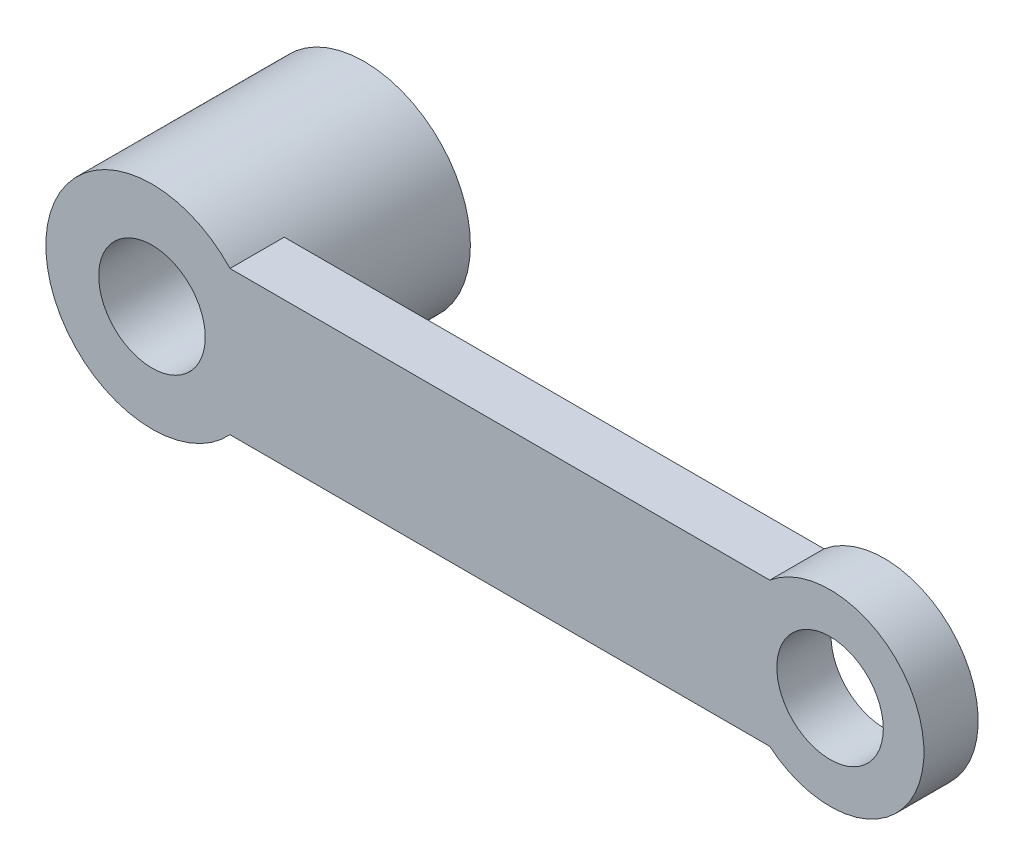
SolidWorks part; units mm, degrees
ref_plane "Alzado" through (0, 0, 0) normal (0, 0, 1) x (1, 0, 0)
ref_plane "Planta" through (0, 0, 0) normal (0, 1, 0) x (1, 0, 0)
ref_plane "Vista lateral" through (0, 0, 0) normal (1, 0, 0) x (0, 0, -1)
sketch "Croquis1" plane through (0, 0, 0) normal (0, 0, 1) x (1, 0, 0)
  line L1 (7.478, 6.9) -> (59.2216, 6.9)
  line L3 (7.478, -6.9) -> (59.2216, -6.9)
  circle A0 centre (0, 0) radius 5.105
  circle A1 centre (0, 0) radius 10.175
  circle A2 centre (65, 0) radius 5.105
  circle A3 centre (65, 0) radius 9
  point P11 (0, 0)
  point P12 (0, 0)
  dimension "D2" = 10.21
  dimension "D3" = 18
  dimension "D4" = 20.35
  dimension "D5" = 10.21
  dimension "D1" = 65
  dimension "D6" = 13.8
  dimension "D7" = 59.2216
  dimension "D8" = 51.7436
extrude "Saliente-Extruir1" add sketch "Croquis1" along normal blind 5.2 contours A3 L1 A1 L3 | A3 | A2 | A1 | A0 region at (33.1589, 0, 0)
extrude "Saliente-Extruir2" add sketch "Croquis1<3>" against normal blind 15.15 contours A1 A0 region at (9.2088, 3.5994, 0)
sketch "Croquis1<3>" plane through (0, 0, 0) normal (0, 0, 1) x (1, 0, 0) same geometry as "Croquis1"
